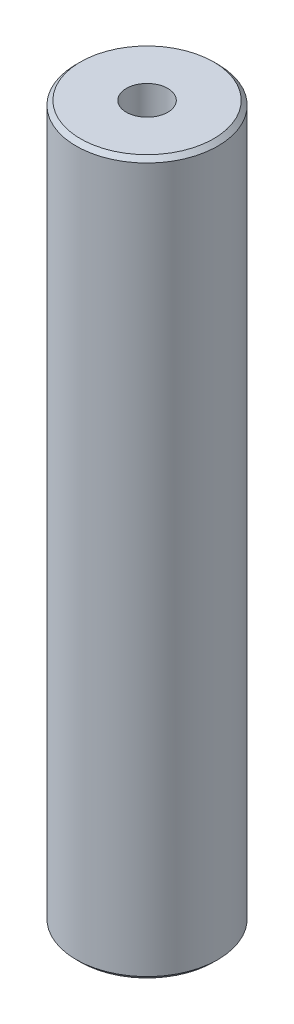
SolidWorks part; units mm, degrees
ref_plane "Front Plane" through (0, 0, 0) normal (0, 0, 1) x (1, 0, 0)
ref_plane "Top Plane" through (0, 0, 0) normal (0, 1, 0) x (1, 0, 0)
ref_plane "Right Plane" through (0, 0, 0) normal (1, 0, 0) x (0, 0, -1)
sketch "Sketch1" plane through (0, 0, 0) normal (0, 1, 0) x (1, 0, 0)
  circle A0 centre (0, 0) radius 17.5
  dimension "SHAFT_OD" = 35
extrude "Boss-Extrude1" add sketch "Sketch1" along normal blind 176.1491
sketch "Sketch2" plane through (0, 0, 0) normal (0, 1, 0) x (1, 0, 0)
  circle A0 centre (0, 0) radius 5.1176
  dimension "BORE_D" = 10.2353
extrude "Cut-Extrude1" cut sketch "Sketch2" along normal through all
chamfer "Chamfer1" distance 1.0466 angle 45 2 edges at (0, 176.1491, 17.5) (0, 0, 17.5)
